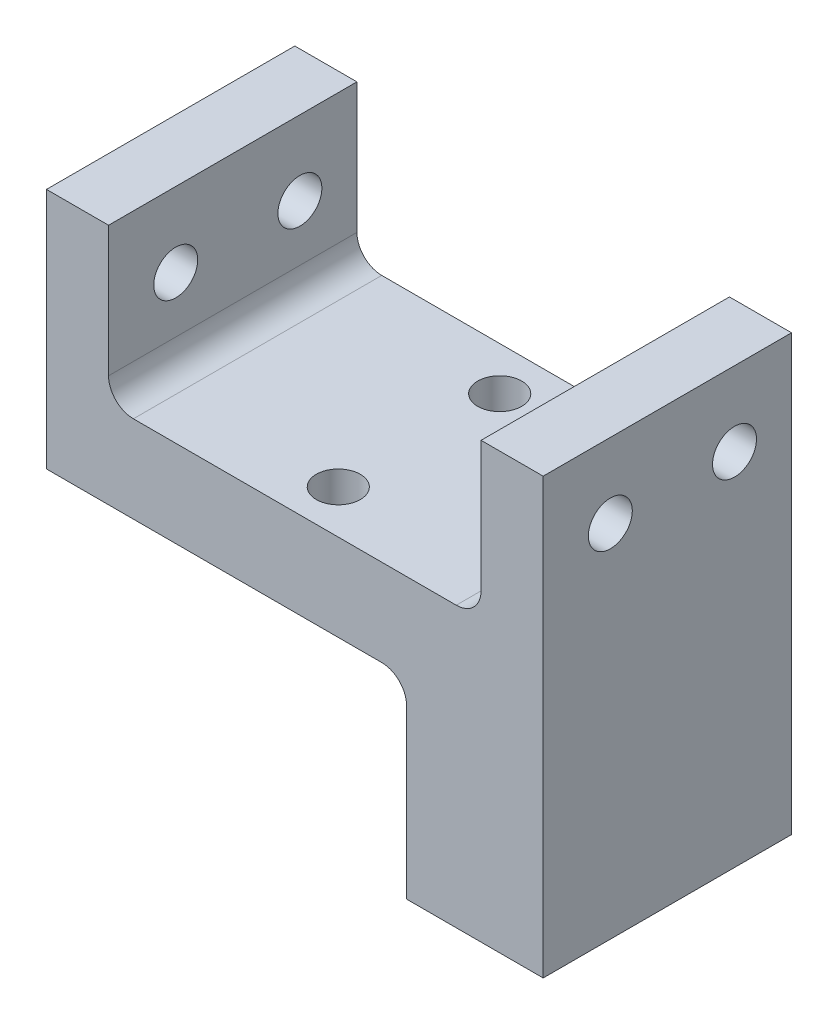
SolidWorks part; units mm, degrees
ref_plane "Front Plane" through (0, 0, 0) normal (0, 0, 1) x (1, 0, 0)
ref_plane "Top Plane" through (0, 0, 0) normal (0, 1, 0) x (1, 0, 0)
ref_plane "Right Plane" through (0, 0, 0) normal (1, 0, 0) x (0, 0, -1)
sketch "Sketch1" plane through (0, 0, 0) normal (0, 1, 0) x (1, 0, 0)
  line L1 (-25.4, -12.7) -> (25.4, -12.7)
  line L2 (-25.4, -12.7) -> (-25.4, 12.7)
  line L3 (-25.4, 12.7) -> (25.4, 12.7)
  line L4 (25.4, -12.7) -> (25.4, 12.7)
  line L5 (-25.4, -12.7) -> (25.4, 12.7) construction
  line L6 (-25.4, 12.7) -> (25.4, -12.7) construction
  point P0 (0, 0)
  dimension "D1" = 25.4
  dimension "D2" = 50.8
extrude "Boss-Extrude1" add sketch "Sketch1" along normal blind 44.45
sketch "Sketch2" plane through (0, 44.45, 0) normal (0, 1, 0) x (1, 0, 0)
  line L0 (25.4, -12.7) -> (25.4, 12.7) construction
  line L1 (-25.4, -152.4) -> (25.4, -152.4)
  line L2 (-25.4, -152.4) -> (-25.4, 0)
  line L3 (-25.4, 0) -> (25.4, 0)
  line L4 (25.4, -152.4) -> (25.4, 0)
  line L5 (-25.4, -152.4) -> (25.4, 0) construction
  line L6 (-25.4, 0) -> (25.4, -152.4) construction
  line L7 (-25.4, 12.7) -> (-25.4, -12.7) construction
  line L8 (25.4, 12.7) -> (-25.4, 12.7) construction
  point P0 (0, -76.2)
  dimension "D1" = 152.4
  dimension "D2" = 12.7
sketch "Sketch3" plane through (0, 0, -12.7) normal (0, 0, -1) x (-1, 0, 0)
  line L0 (-22.225, 5.9185) -> (22.225, 5.9185) construction
  point P2 (0, 5.9185)
  dimension "D1" = 44.45
sketch "Sketch8" plane through (0, 0, 12.7) normal (0, 0, 1) x (1, 0, 0)
  line L1 (-11.43, -19.685) -> (11.43, -19.685)
  line L2 (-11.43, -19.685) -> (-11.43, 19.685)
  line L3 (-11.43, 19.685) -> (11.43, 19.685)
  line L4 (11.43, -19.685) -> (11.43, 19.685)
  line L5 (-11.43, -19.685) -> (11.43, 19.685) construction
  line L6 (-11.43, 19.685) -> (11.43, -19.685) construction
  line L7 (-19.05, 28.575) -> (19.05, 28.575)
  line L8 (-19.05, 28.575) -> (-19.05, 60.325)
  line L9 (-19.05, 60.325) -> (19.05, 60.325)
  line L10 (19.05, 28.575) -> (19.05, 60.325)
  line L11 (-19.05, 28.575) -> (19.05, 60.325) construction
  line L12 (-19.05, 60.325) -> (19.05, 28.575) construction
  line L13 (-11.43, 19.685) -> (-32.668, 19.685)
  line L14 (-11.43, 19.685) -> (-11.43, -19.685)
  line L15 (-11.43, -19.685) -> (-32.668, -19.685)
  line L16 (-32.668, 19.685) -> (-32.668, -19.685)
  point P0 (0, 0)
  point P6 (0, 44.45)
  line M5 (-25.4, 0) -> (25.4, 0)
  line M7 (25.4, 44.45) -> (-25.4, 44.45)
  line M8 (-25.4, 44.45) -> (-25.4, 0)
  dimension "D1" = 22.86
  dimension "155" = 39.37
  dimension "D3" = 31.75
  dimension "D4" = 38.1
extrude "Cut-Extrude1" cut sketch "Sketch8" against normal through all contours L2 L13 M8 M5 | L4 L3 L2 M5 | L7 L10 L8 M7 region at (0, 36.5125, 12.7) region at (-18.415, 9.8425, 12.7) region at (0, 9.8425, 12.7)
sketch "Sketch9" plane through (25.4, 0, 0) normal (1, 0, 0) x (0, 0, -1)
  line L0 (0, 44.45) -> (-152.4, 44.45) construction
  line L1 (-5.8318, 36.83) -> (6.8682, 36.83) construction
  point P0 (6.8682, 36.83)
  point P16 (-5.8318, 36.83)
  dimension "D1" = 7.62
  dimension "D2" = 12.7
hole_wizard "#8 Clearance Hole3" positions "Sketch9" profile "Sketch10" hole size "#8" standard "ANSI Inch" end condition through all
sketch "Sketch10" plane through (25.4, 36.83, -6.8682) normal (0, 1, 0) x (0, 0, -1)
  line L0 (0, 0) -> (0, 50.8)
  line L1 (0, 50.8) -> (2.2479, 50.8)
  line L2 (2.2479, 50.8) -> (2.2479, 0)
  line L5 (2.2479, 0) -> (0, 0)
  line L11 (0, -6.35) -> (0, 107.95) construction
  dimension "Thru Hole Dia." = 4.4958
  dimension "Thru Hole Depth" = 50.8
hole_wizard "#8 Clearance Hole2" positions "Sketch13" profile "Sketch14" hole size "#8" standard "ANSI Inch" end condition through all
sketch "Sketch13" plane through (0, 28.575, 0) normal (0, 1, 0) x (1, 0, 0)
  line L0 (0, 8.255) -> (0, -8.255) construction
  point P0 (0, 8.255)
  point P2 (0, -8.255)
  point P6 (0, 0)
  dimension "D1" = 16.51
sketch "Sketch14" plane through (0, 28.575, -8.255) normal (1, 0, 0) x (0, 0, 1)
  line L0 (0, 0) -> (0, 28.575)
  line L1 (0, 28.575) -> (2.2479, 28.575)
  line L2 (2.2479, 28.575) -> (2.2479, 0)
  line L5 (2.2479, 0) -> (0, 0)
  line L11 (0, -6.35) -> (0, 107.95) construction
  dimension "Thru Hole Dia." = 4.4958
  dimension "Thru Hole Depth" = 28.575
hole_wizard "1/8 (0.18) Dowel Hole1" positions "Sketch15" profile "Sketch16" hole size "1/8" standard "ANSI Inch"
sketch "Sketch15" plane through (11.43, 0, 0) normal (-1, 0, 0) x (0, 0, 1)
  line L0 (-45.5977, 8.509) -> (-45.5977, 3.683) construction
  line L1 (-45.5977, 6.096) -> (2.9163, 6.096) construction
  point P0 (2.9163, 6.096)
sketch "Sketch16" plane through (11.43, 6.096, 2.9163) normal (0, 1, 0) x (0, 0, 1)
  line L0 (0, 0) -> (0, 8.9936)
  line L1 (0, 8.9936) -> (2.286, 7.62)
  line L2 (2.286, 7.62) -> (2.286, 0)
  line L5 (2.286, 0) -> (0, 0)
  line L10 (0, 8.9936) -> (-2.286, 7.62) construction
  line L11 (0, -6.35) -> (0, 107.95) construction
  dimension "Hole Dia." = 4.572
  dimension "Hole Depth" = 7.62
  dimension "Drill Angle" = 118
fillet "Fillet1" radius 2.54 3 edges at (11.43, 19.685, 0) (-19.05, 28.575, 0) (19.05, 28.575, 0)
